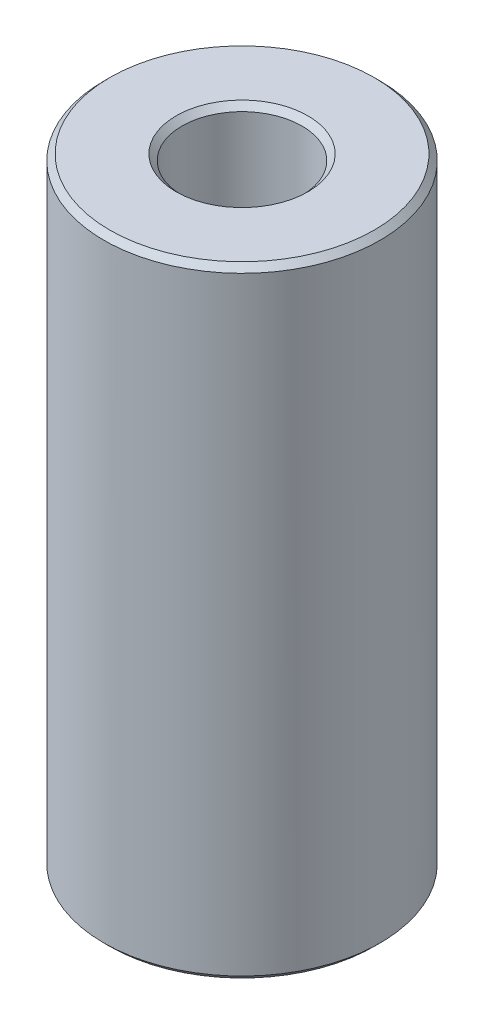
SolidWorks part; units mm, degrees
ref_plane "Front Plane" through (0, 0, 0) normal (0, 0, 1) x (1, 0, 0)
ref_plane "Top Plane" through (0, 0, 0) normal (0, 1, 0) x (1, 0, 0)
ref_plane "Right Plane" through (0, 0, 0) normal (1, 0, 0) x (0, 0, -1)
sketch "Sketch1" plane through (0, 0, 0) normal (0, 1, 0) x (1, 0, 0)
  circle A0 centre (0, 0) radius 57.5
  dimension "SLEEVE_OD" = 115
extrude "Boss-Extrude1" add sketch "Sketch1" along normal blind 258.3384
sketch "Sketch2" plane through (0, 0, 0) normal (0, 1, 0) x (1, 0, 0)
  circle A0 centre (0, 0) radius 24.9877
  dimension "BORE_D" = 49.9753
extrude "Cut-Extrude1" cut sketch "Sketch2" along normal through all
chamfer "Chamfer1" distance 2.4512 angle 45 4 edges at (0, 258.3384, 24.9877) (0, 0, 24.9877) (0, 0, 57.5) (0, 258.3384, 57.5)
